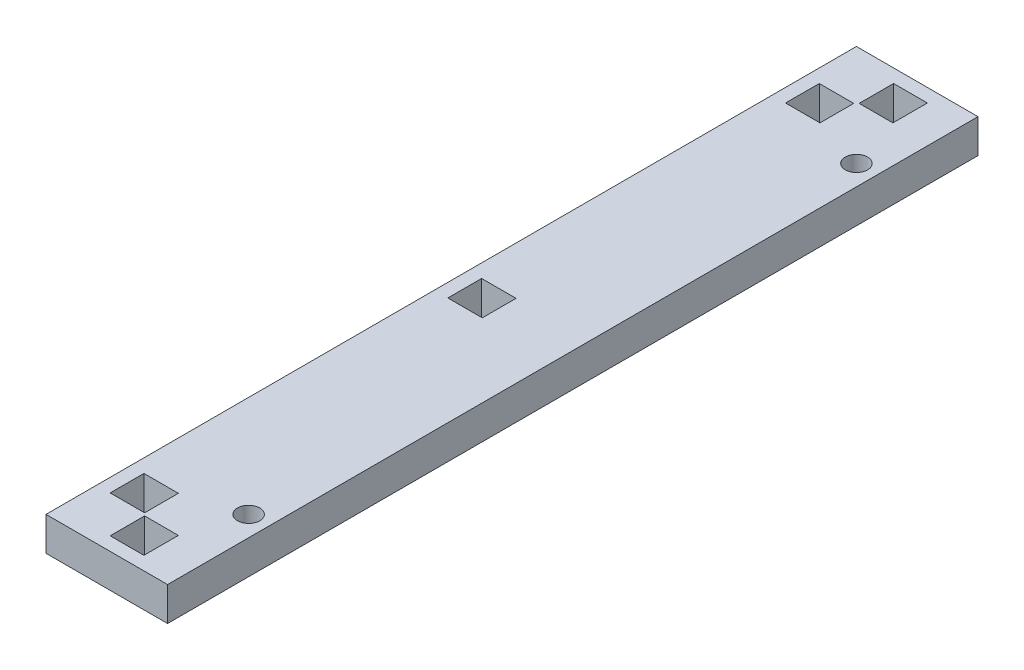
SolidWorks part; units mm, degrees
ref_plane "Front" through (0, 0, 0) normal (0, 0, 1) x (1, 0, 0)
ref_plane "Top" through (0, 0, 0) normal (0, 1, 0) x (1, 0, 0)
ref_plane "Right" through (0, 0, 0) normal (1, 0, 0) x (0, 0, -1)
sketch "Sketch1" plane through (0, 0, 0) normal (0, 1, 0) x (1, 0, 0)
  line L1 (-9, -60) -> (9, -60)
  line L2 (-9, -60) -> (-9, 60)
  line L3 (-9, 60) -> (9, 60)
  line L4 (9, -60) -> (9, 60)
  line L5 (-9, -60) -> (9, 60) construction
  line L6 (-9, 60) -> (9, -60) construction
  point P0 (0, 0)
  dimension "D1" = 18
  dimension "D2" = 120
extrude "Boss-Extrude1" add sketch "Sketch1" along normal blind 5
hole_wizard "Ø3.3 (3.3) Diameter Hole1" positions "Sketch3" profile "Sketch2" hole size "Ø3.3" standard "ANSI Metric" end condition through all
sketch "Sketch3" plane through (0, 5, 0) normal (0, 1, 0) x (1, 0, 0)
  line L2 (6, -45) -> (6, 45)
  line L7 (-9, 60) -> (-9, -60) construction
  line L9 (9, 60) -> (-9, 60) construction
  point P0 (6, 45)
  point P6 (6, -45)
  dimension "D1" = 90
  dimension "D2" = 15
  dimension "D3" = 15
sketch "Sketch2" plane through (6, 5, -45) normal (1, 0, 0) x (0, 0, 1)
  line L0 (0, 0) -> (0, 5)
  line L1 (0, 5) -> (1.65, 5)
  line L2 (1.65, 5) -> (1.65, 0)
  line L5 (1.65, 0) -> (0, 0)
  line L11 (0, -6.35) -> (0, 107.95) construction
  dimension "Thru Hole Dia." = 3.3
  dimension "Thru Hole Depth" = 5
sketch "Sketch5" plane through (0, 5, 0) normal (0, 1, 0) x (1, 0, 0)
  line L0 (-9, 60) -> (-9, -60) construction
  line L1 (-7, 52.5) -> (-1.9, 52.5)
  line L2 (-7, 52.5) -> (-7, 47.5)
  line L3 (-7, 47.5) -> (-1.9, 47.5)
  line L4 (-1.9, 52.5) -> (-1.9, 47.5)
  line L5 (-7, -47.5) -> (-1.9, -47.5)
  line L6 (-7, -47.5) -> (-7, -52.5)
  line L7 (-7, -52.5) -> (-1.9, -52.5)
  line L8 (-1.9, -47.5) -> (-1.9, -52.5)
  line L9 (-1.5, -52.9) -> (3.5, -52.9)
  line L10 (-1.5, -52.9) -> (-1.5, -58)
  line L11 (-1.5, -58) -> (3.5, -58)
  line L12 (3.5, -52.9) -> (3.5, -58)
  line L17 (-1.5, 58) -> (3.5, 58)
  line L18 (-1.5, 58) -> (-1.5, 52.9)
  line L19 (-1.5, 52.9) -> (3.5, 52.9)
  line L20 (3.5, 58) -> (3.5, 52.9)
  line L33 (9, 60) -> (-9, 60) construction
  line L35 (-9, -60) -> (9, -60) construction
  line L37 (-7, 2.5) -> (-1.9, 2.5)
  line L38 (-7, 2.5) -> (-7, -2.5)
  line L39 (-7, -2.5) -> (-1.9, -2.5)
  line L40 (-1.9, 2.5) -> (-1.9, -2.5)
  dimension "D1" = 2
  dimension "D2" = 95
  dimension "D3" = 105
  dimension "D4" = 7.5
  dimension "D5" = 5.1
  dimension "D6" = 5
  dimension "D8" = 2
  dimension "D9" = 5.1
  dimension "D10" = 2
  dimension "D11" = 5.1
  dimension "D14" = 7.5
  dimension "D15" = 5
  dimension "D16" = 45
extrude "Cut-Extrude1" cut sketch "Sketch5" against normal through all
